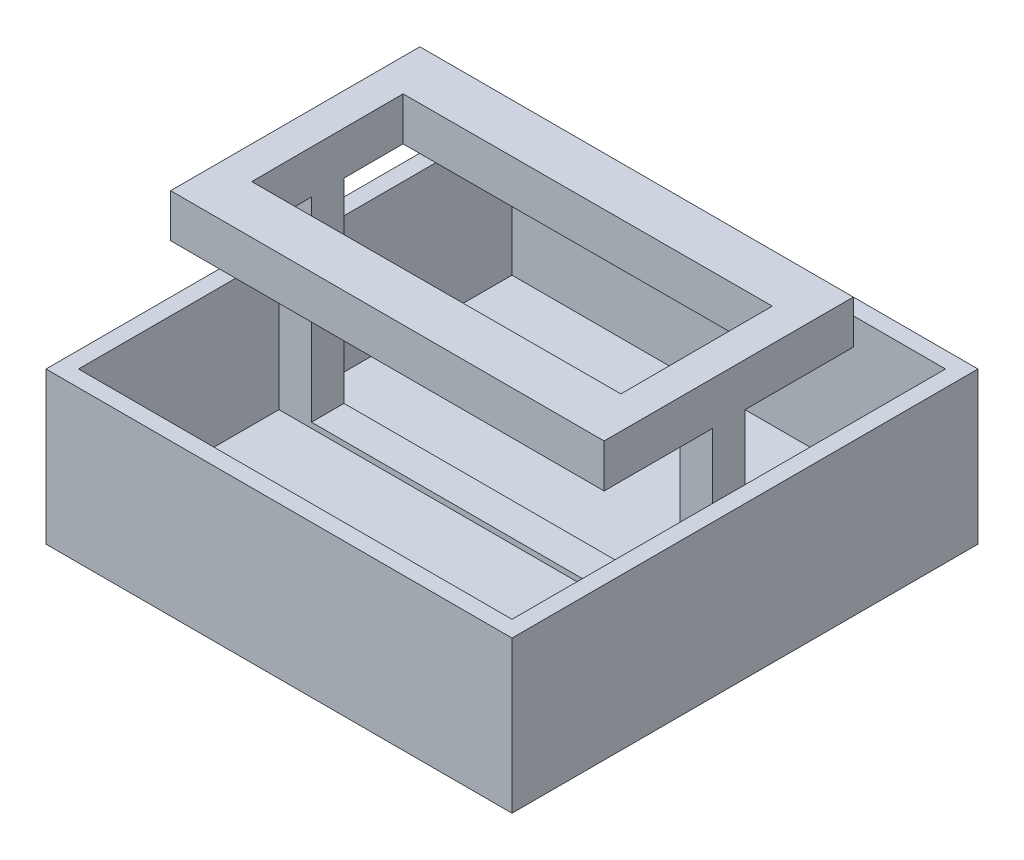
SolidWorks part; units mm, degrees
ref_plane "Front Plane" through (0, 0, 0) normal (0, 0, 1) x (1, 0, 0)
ref_plane "Top Plane" through (0, 0, 0) normal (0, 1, 0) x (1, 0, 0)
ref_plane "Right Plane" through (0, 0, 0) normal (1, 0, 0) x (0, 0, -1)
sketch "Sketch1" plane through (0, 0, 0) normal (0, 1, 0) x (1, 0, 0)
  line L0 (-10.75, 10.75) -> (-10.75, -10.75)
  line L1 (-10, 10) -> (10, 10)
  line L2 (-10, 10) -> (-10, -10)
  line L3 (-10, -10) -> (10, -10)
  line L4 (10, 10) -> (10, -10)
  line L5 (-10, 10) -> (10, -10) construction
  line L6 (-10, -10) -> (10, 10) construction
  line L7 (-10.75, -10.75) -> (10.75, -10.75)
  line L8 (10.75, 10.75) -> (10.75, -10.75)
  line L9 (-10.75, 10.75) -> (10.75, 10.75)
  line L11 (-10, 0.75) -> (10, 0.75)
  line L12 (-10, 0.75) -> (-10, -0.75)
  line L13 (-10, -0.75) -> (10, -0.75)
  line L14 (10, 0.75) -> (10, -0.75)
  line L15 (-10, 0.75) -> (10, -0.75) construction
  line L16 (-10, -0.75) -> (10, 0.75) construction
  point P0 (0, 0)
  point P10 (0, 0)
  dimension "D1" = 20
  dimension "D2" = 20
  dimension "D4" = 1.5
  dimension "D3" = 0.75
extrude "Boss-Extrude1" add sketch "Sketch1" along normal blind 7 contours L9 L0 L7 L8 L1 L4 L3 L2 region at (0, 0, -10.4459)
extrude "Boss-Extrude2" add sketch "Sketch1<3>" along normal blind 0.75 contours L13 L2 L3 L4 | L2 L13 L4 L11 | L2 L11 L4 L1 region at (0, 0, -5.375) region at (0, 0, 0) region at (0, 0, 5.375)
sketch "Sketch1<3>" plane through (0, 0, 0) normal (0, 1, 0) x (1, 0, 0) same geometry as "Sketch1"
extrude "Boss-Extrude3" add sketch "Sketch1<4>" along normal blind 12 contours L2 L13 L4 L11 region at (0, 0, 0)
sketch "Sketch1<4>" plane through (0, 0, 0) normal (0, 1, 0) x (1, 0, 0) same geometry as "Sketch1"
sketch "Sketch3" plane through (0, 0, -0.75) normal (0, 0, -1) x (-1, 0, 0)
  line L0 (-10, 12) -> (-10, 7) construction
  line L1 (-10, 12) -> (10, 12)
  line L2 (-10, 12) -> (-10, 10)
  line L3 (-10, 10) -> (10, 10)
  line L4 (10, 12) -> (10, 10)
  line L5 (-10, 12) -> (10, 10) construction
  line L6 (-10, 10) -> (10, 12) construction
  line L7 (10, 12) -> (-10, 12) construction
  point P0 (0, 11)
  point P5 (-10, 12)
  point P10 (10, 12)
  dimension "D1" = 2
extrude "Boss-Extrude4" add sketch "Sketch3" along normal blind 5 and the other way blind 6.5
sketch "Sketch4" plane through (0, 12, 0) normal (0, 1, 0) x (1, 0, 0)
  line L0 (-8.5072, 3.4826) -> (8.4928, 3.5174)
  line L1 (-8.5072, 3.4826) -> (-8.4928, -3.5174)
  line L2 (8.4928, 3.5174) -> (8.5072, -3.4826)
  line L3 (-8.4928, -3.5174) -> (8.5072, -3.4826)
  line L4 (-8.5072, 3.4826) -> (8.5072, -3.4826) construction
  line L5 (8.4928, 3.5174) -> (-8.4928, -3.5174) construction
  point P0 (7.6051, 2.4756)
  point P1 (0, 0)
  dimension "D1" = 7
  dimension "D2" = 17
extrude "Cut-Extrude1" cut sketch "Sketch4" against normal blind 11
